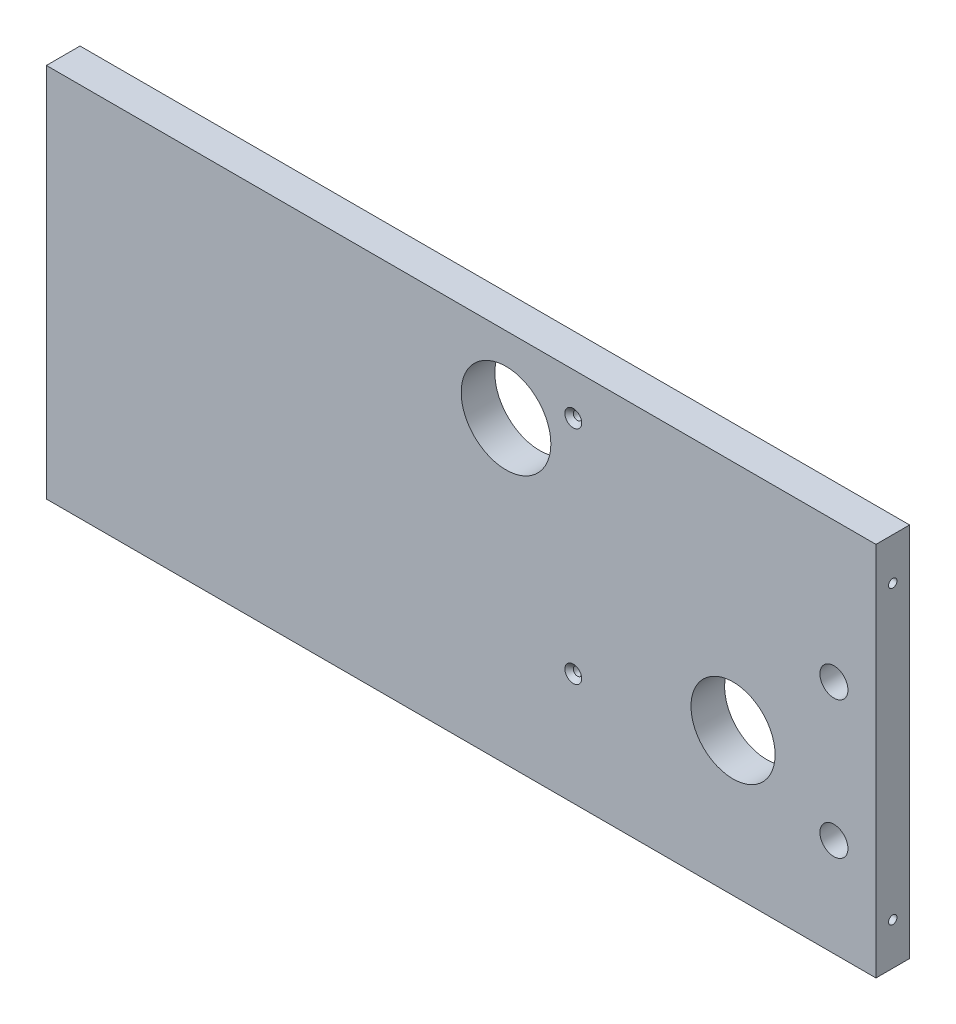
SolidWorks part; units mm, degrees
ref_plane "Front Plane" through (0, 0, 0) normal (0, 0, 1) x (1, 0, 0)
ref_plane "Top Plane" through (0, 0, 0) normal (0, 1, 0) x (1, 0, 0)
ref_plane "Right Plane" through (0, 0, 0) normal (1, 0, 0) x (0, 0, -1)
sketch "Sketch1" plane through (0, 0, 0) normal (0, 0, 1) x (1, 0, 0)
  line L0 (293.1891, 163.9309) -> (293.1891, -7.8066) construction
  line L5 (12.1891, 0) -> (308.1891, 0)
  line L6 (12.1891, 0) -> (12.1891, 134)
  line L7 (12.1891, 134) -> (308.1891, 134)
  line L12 (308.1891, 0) -> (308.1891, 134)
  circle A0 centre (257.1891, 51) radius 15
  circle A5 centre (176.1891, 107) radius 16
  circle A6 centre (293.1891, 84) radius 5
  circle A11 centre (200.1891, 119) radius 1.5
  circle A12 centre (200.1891, 40) radius 1.5
  circle A13 centre (293.1891, 35) radius 5
  point P10 (0, 0)
  dimension "D3" = 27
  dimension "D14" = 3
  dimension "D15" = 134
  dimension "D18" = 51
  dimension "D1" = 32
  dimension "D2" = 30
  dimension "D9" = 15
  dimension "D21" = 3
  dimension "D5" = 10
  dimension "D6" = 10
  dimension "D4" = 51
  dimension "D7" = 35
  dimension "D8" = 50
  dimension "D19" = 132
  dimension "D20" = 296
  dimension "D22" = 40
  dimension "D23" = 15
  dimension "D24" = 188
  dimension "D25" = 188
extrude "Boss-Extrude1" add sketch "Sketch1" along normal blind 12
sketch "Sketch2" plane through (0, 0, 0) normal (1, 0, 0) x (0, 0, -1)
  line L0 (-6, 134) -> (-6, 0) construction
  line L1 (-12, 134) -> (0, 134) construction
  line L2 (-12, 0) -> (0, 0) construction
  circle A0 centre (-6, 119) radius 1.5
  circle A1 centre (-6, 15) radius 1.5
  dimension "D1" = 3
  dimension "D2" = 3
  dimension "D3" = 15
  dimension "D4" = 15
extrude "Cut-Extrude1" cut sketch "Sketch2" along normal blind 20 from surface starting at face at (12.1891, 67, 6)
extrude "Cut-Extrude2" cut sketch "Sketch2<2>" against normal blind 20 from surface starting at face at (308.1891, 67, 6)
sketch "Sketch2<2>" plane through (0, 0, 0) normal (1, 0, 0) x (0, 0, -1) same geometry as "Sketch2"
sketch "Sketch4" plane through (0, 0, 0) normal (0, 0, 1) x (1, 0, 0)
  circle A0 centre (200.1891, 119) radius 3
  circle A1 centre (200.1891, 40) radius 3
  dimension "D1" = 6
  dimension "D2" = 6
extrude "Cut-Extrude4" cut sketch "Sketch4" against normal blind 3 draft 45 from surface starting at face at (160.1891, 67, 12)
sketch "Sketch5" plane through (0, 0, 0) normal (0, 0, 1) x (1, 0, 0)
  circle A0 centre (221.1891, 122) radius 1.5
  circle A1 centre (255.1891, 122) radius 1.5
  circle A2 centre (221.1891, 92) radius 1.5
  circle A3 centre (255.1891, 92) radius 1.5
  dimension "D1" = 3
  dimension "D2" = 3
  dimension "D3" = 3
  dimension "D4" = 3
  dimension "D5" = 53
  dimension "D6" = 53
  dimension "D7" = 87
  dimension "D8" = 87
  dimension "D9" = 12
  dimension "D10" = 12
  dimension "D11" = 42
  dimension "D12" = 42
extrude "Cut-Extrude5" cut sketch "Sketch5" along normal blind 10 from surface starting at face at (201.6891, 40, 0)
